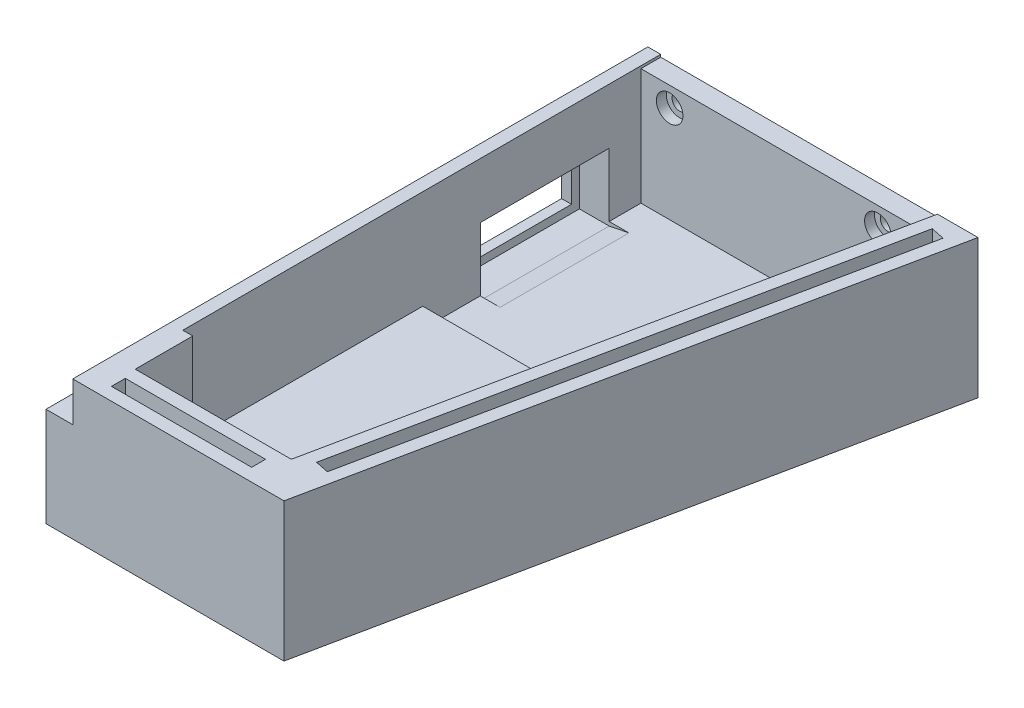
SolidWorks part; units mm, degrees
ref_plane "Front Plane" through (0, 0, 0) normal (1, 0, 0) x (0, 1, 0)
ref_plane "Top Plane" through (0, 0, 0) normal (0, 0, 1) x (0, 1, 0)
ref_plane "Right Plane" through (0, 0, 0) normal (0, 1, 0) x (-1, 0, 0)
sketch "Sketch1" plane through (0, 0, 0) normal (0, 1, 0) x (-1, 0, 0)
  line L0 (-13.4363, 2.5951) -> (16.5637, 147.5951)
  line L1 (-13.4363, -4.9049) -> (-8.4363, -4.9049)
  line L2 (-13.4363, -4.9049) -> (-13.4363, 2.5951)
  line L3 (-13.4363, 2.5951) -> (-8.4363, 2.5951)
  line L4 (-8.4363, -4.9049) -> (-8.4363, 2.5951)
  line L13 (-13.4363, 2.5951) -> (16.5637, 147.5951)
  line L14 (-13.4363, 2.5951) -> (-3.6437, 0.569)
  line L15 (-13.4363, 2.5951) -> (66.5637, 2.5951) construction
  line L16 (-13.4363, 2.5951) -> (-13.4363, 137.5951) construction
  line L17 (-13.4363, 137.5951) -> (66.5637, 137.5951) construction
  line L18 (66.5637, 2.5951) -> (66.5637, 137.5951) construction
  line L19 (66.5637, 137.5951) -> (16.5637, 137.5951)
  line L20 (66.5637, 137.5951) -> (66.5637, 147.5951)
  line L21 (66.5637, 147.5951) -> (16.5637, 147.5951)
  line L22 (16.5637, 137.5951) -> (16.5637, 147.5951)
  line L23 (16.5637, 147.5951) -> (26.3563, 145.569)
  line L24 (-3.6437, 0.569) -> (26.3563, 145.569)
  line L25 (-8.4363, 2.5951) -> (-3.2246, 2.5951)
  line L27 (-3.2246, 2.5951) -> (66.5637, 2.5951)
  line L28 (-3.2246, 2.5951) -> (-3.2246, 7.5951)
  line L29 (-3.2246, 7.5951) -> (66.5637, 7.5951)
  line L30 (66.5637, 2.5951) -> (66.5637, 7.5951)
  line L35 (66.5637, 147.5951) -> (76.5637, 147.5951)
  line L36 (66.5637, 147.5951) -> (66.5637, 2.5951)
  line L37 (66.5637, 2.5951) -> (76.5637, 2.5951)
  line L38 (76.5637, 147.5951) -> (76.5637, 2.5951)
  dimension "D1" = 7.5
  dimension "D3" = 135
  dimension "D4" = 80
  dimension "D5" = 10
  dimension "D7" = 10
  dimension "D9" = 5
  dimension "D8" = 10
  dimension "D6" = 50
extrude "Boss-Extrude1" add sketch "Sketch1" along normal blind 35 contours L24 L19 L20 L21 L23 | L19 L24 L23 L22 | L28 L29 L24 L19 L22 L0 L3 L25 | L38 L35 L20 L36 L30 L37 | L29 L28 L24 | L27 L30 L29 L24 region at (-5.7274, 0, 70.7433) region at (-20.91, 0, 142.2574) region at (-45.5816, 0, 142.6608) region at (-71.5637, 0, 75.0951) region at (2.8797, 0, 5.9284) region at (-31.9275, 0, 5.0889)
sketch "Sketch3" plane through (0, 0, 0) normal (0, -1, 0) x (1, 0, 0)
  line L0 (-76.5637, 147.5951) -> (-16.5637, 147.5951)
  line L1 (-16.5637, 147.5951) -> (13.4363, 2.5951)
  line L2 (13.4363, 2.5951) -> (-76.5637, 2.5951)
  line L3 (-76.5637, 2.5951) -> (-76.5637, 147.5951)
extrude "Boss-Extrude2" add sketch "Sketch3" against normal blind 10
sketch "Sketch4" plane through (0, 35, 0) normal (0, 1, 0) x (-1, 0, 0)
  line L0 (24.7065, 137.5951) -> (-3.2246, 2.5951)
  line L1 (24.7065, 137.5951) -> (66.5637, 137.5951)
  line L2 (24.7065, 137.5951) -> (24.7065, 147.5951)
  line L3 (24.7065, 147.5951) -> (66.5637, 147.5951)
  line L4 (66.5637, 137.5951) -> (66.5637, 147.5951)
  line L5 (24.7065, 137.5951) -> (14.9139, 139.6211)
  line L6 (-3.2246, 2.5951) -> (-13.0172, 4.6211)
  line L7 (14.9139, 139.6211) -> (-13.0172, 4.6211)
  line L8 (-13.4363, 2.5951) -> (76.5637, 2.5951) construction
  line L9 (20.8654, 135.071) -> (-5.7487, 6.4361)
  line L10 (-5.7487, 6.4361) -> (-9.1761, 7.1453)
  line L11 (17.438, 135.7801) -> (-9.1761, 7.1453)
  line L12 (20.8654, 135.071) -> (17.438, 135.7801)
  line L13 (27.9565, 140.8451) -> (27.9565, 144.3451)
  line L14 (27.9565, 144.3451) -> (63.3137, 144.3451)
  line L15 (63.3137, 140.8451) -> (63.3137, 144.3451)
  line L16 (27.9565, 140.8451) -> (63.3137, 140.8451)
  line L17 (76.5637, 147.5951) -> (16.5637, 147.5951) construction
  line L18 (17.438, 135.7801) -> (19.8825, 147.5951)
  line L19 (-2.1901, 7.5951) -> (24.7065, 137.5951) construction
  line L20 (20.8654, 135.071) -> (23.4566, 147.5951)
  line L21 (23.4566, 147.5951) -> (19.8825, 147.5951)
  line L22 (27.9565, 144.3451) -> (19.2101, 144.3451)
  line L23 (19.2101, 144.3451) -> (18.4859, 140.8451)
  line L24 (18.4859, 140.8451) -> (27.9565, 140.8451)
  line L25 (-13.4363, 2.5951) -> (16.5637, 147.5951) construction
  point P4 (-13.4363, 2.5951)
  point P5 (-3.1129, 2.5951)
  dimension "D1" = 3.25
extrude "Cut-Extrude1" cut sketch "Sketch4" against normal blind 10 contours L9 L12 L11 L10 | L13 L16 L15 L14 region at (-45.6351, 35, 142.5951) region at (-5.8447, 35, 71.1081)
sketch "Sketch5" plane through (0, 35, -3.0299) normal (0, -1, 0) x (1, 0, 0)
  line L5 (13.4363, 5.625) -> (-76.5637, 5.625) construction
  line L6 (-66.5637, 10.625) -> (2.1901, 10.625)
  line L7 (-66.5637, 10.625) -> (-66.5637, 5.625)
  line L8 (-66.5637, 5.625) -> (2.1901, 5.625)
  line L9 (2.1901, 10.625) -> (2.1901, 5.625)
  line L10 (2.1901, 10.625) -> (3.2246, 5.625)
  line L11 (2.1901, 10.625) -> (-24.7065, 140.625) construction
  line L12 (3.2246, 5.625) -> (2.1901, 5.625)
  line M9 (-66.5637, 10.625) -> (2.1901, 10.625)
  line M14 (13.4363, 5.625) -> (-76.5637, 5.625)
extrude "Cut-Extrude2" cut sketch "Sketch5" along normal blind 0.625 contours L9 L10 M14 | L9 L7 M9 M14 region at (-32.1868, 35, 5.0951) region at (2.5349, 35, 4.2617)
sketch "Sketch6" plane through (0, 0, 7.5951) normal (0, 0, 1) x (1, 0, 0)
  line L1 (-66.5637, 34.375) -> (-59.3137, 34.375) construction
  line L2 (-66.5637, 34.375) -> (-66.5637, 29.375) construction
  line L3 (-66.5637, 29.375) -> (-59.3137, 29.375) construction
  line L4 (-59.3137, 34.375) -> (-59.3137, 29.375) construction
  circle A0 centre (-59.3137, 29.375) radius 1.9
  dimension "D3" = 3.8
  dimension "D1" = 7.25
extrude "Cut-Extrude3" cut sketch "Sketch6" against normal up to next
sketch "Sketch7" plane through (0, 0, 7.5951) normal (0, 0, 1) x (1, 0, 0)
  circle A0 centre (-59.3137, 29.375) radius 3.35
  dimension "D1" = 6.7
extrude "Cut-Extrude4" cut sketch "Sketch7" against normal blind 2.5
pattern_linear "LPattern1" count 2 spacing 52.5 along (1, 0, 0) of "Cut-Extrude4", "Cut-Extrude3"
sketch "Sketch8" plane through (0, 35, 0) normal (0, 1, 0) x (-1, 0, 0)
  line L0 (76.5637, 147.5951) -> (16.5637, 147.5951) construction
  line L1 (66.5637, 2.5951) -> (69.8137, 2.5951)
  line L2 (66.5637, 2.5951) -> (66.5637, 147.5951)
  line L3 (66.5637, 147.5951) -> (69.8137, 147.5951)
  line L4 (69.8137, 2.5951) -> (69.8137, 147.5951)
  line L5 (66.5637, 2.5951) -> (76.5637, 2.5951) construction
  line L6 (76.5637, 147.5951) -> (73.3137, 147.5951)
  line L7 (76.5637, 147.5951) -> (76.5637, 2.5951)
  line L8 (76.5637, 2.5951) -> (73.3137, 2.5951)
  line L9 (73.3137, 147.5951) -> (73.3137, 2.5951)
  line L11 (73.3137, 2.5951) -> (69.8137, 2.5951)
  line L12 (73.3137, 2.5951) -> (73.3137, 147.5951)
  line L13 (73.3137, 147.5951) -> (69.8137, 147.5951)
  line L14 (69.8137, 2.5951) -> (69.8137, 147.5951)
  line M8 (66.5637, 2.5951) -> (76.5637, 2.5951)
  line M9 (76.5637, 2.5951) -> (76.5637, 147.5951)
  line M10 (76.5637, 147.5951) -> (16.5637, 147.5951)
  dimension "D1" = 3.25
  dimension "D2" = 3.25
extrude "Cut-Extrude5" cut sketch "Sketch8" against normal blind 10 contours L9 L4 M10 M8 | L9 M10 M8 M9 region at (-71.5637, 35, 75.0951) region at (-74.9387, 35, 75.0951)
sketch "Sketch10" plane through (0, 10, 0) normal (0, 1, 0) x (-1, 0, 0)
  line L9 (66.5637, 7.5951) -> (-2.1901, 7.5951) construction
  line L14 (66.5637, 7.5951) -> (26.5637, 7.5951)
  line L15 (66.5637, 7.5951) -> (66.5637, 62.5951)
  line L16 (66.5637, 62.5951) -> (26.5637, 62.5951)
  line L17 (26.5637, 7.5951) -> (26.5637, 62.5951)
  line L18 (66.5637, 7.5951) -> (66.5637, 2.5951) construction
  line L19 (26.5637, 62.5951) -> (15.1843, 7.5951)
  line L20 (15.1843, 7.5951) -> (26.5637, 7.5951)
  line L21 (-3.2246, 2.5951) -> (24.7065, 137.5951) construction
  line M16 (-2.1901, 7.5951) -> (66.5637, 7.5951)
  line M17 (66.5637, 7.5951) -> (66.5637, 137.5951)
  dimension "D1" = 40
  dimension "D2" = 55
extrude "Cut-Extrude6" cut sketch "Sketch10" against normal blind 5 contours L17 L19 M16 | L17 L16 M16 M17 region at (-46.5637, 10, 35.0951) region at (-22.7706, 10, 25.9284)
sketch "Sketch9" plane through (-76.5637, 0, 0) normal (-1, 0, 0) x (0, -1, 0)
  line L1 (0, 2.5951) -> (-6, 2.5951) construction
  line L2 (0, 2.5951) -> (0, 17.5951) construction
  line L3 (0, 17.5951) -> (-6, 17.5951) construction
  line L4 (-6, 2.5951) -> (-6, 17.5951) construction
  line L5 (-6, 17.5951) -> (-19, 17.5951)
  line L6 (-6, 17.5951) -> (-6, 46.0951)
  line L7 (-6, 46.0951) -> (-19, 46.0951)
  line L8 (-19, 17.5951) -> (-19, 46.0951)
  dimension "D3" = 28.5
  dimension "D4" = 13
extrude "Cut-Extrude7" cut sketch "Sketch9" against normal up to next
sketch "Sketch11" plane through (-66.5637, 0, 0) normal (1, 0, 0) x (0, 1, 0)
  line L0 (4, 48.0951) -> (4, 15.5951)
  line L1 (6, 46.0951) -> (19, 46.0951)
  line L2 (6, 46.0951) -> (6, 17.5951)
  line L3 (6, 17.5951) -> (19, 17.5951)
  line L4 (19, 46.0951) -> (19, 17.5951)
  line L5 (4, 15.5951) -> (21, 15.5951)
  line L6 (21, 48.0951) -> (21, 15.5951)
  line L7 (4, 48.0951) -> (21, 48.0951)
  dimension "D1" = 2
extrude "Cut-Extrude8" cut sketch "Sketch11" against normal blind 7.5
chamfer "Chamfer1" distance 1 distance2 5 1 edges at (-66.5637, 5, 31.8451) first distance on face at (-66.5637, 4.5, 31.8451)
sketch "Sketch14" plane through (-66.5637, 0, 0) normal (1, 0, 0) x (0, 1, 0)
  line L0 (10, 62.5951) -> (10, 137.5951) construction
  line L1 (35, 137.5951) -> (10, 137.5951)
  line L2 (35, 137.5951) -> (35, 123.0951)
  line L3 (35, 123.0951) -> (10, 123.0951)
  line L4 (10, 137.5951) -> (10, 123.0951)
  dimension "D1" = 14.5
extrude "Boss-Extrude3" add sketch "Sketch14" along normal blind 2.5
sketch "Sketch13" plane through (-69.8137, 0, 0) normal (-1, 0, 0) x (0, -1, 0)
  line L1 (-25, 147.5951) -> (-30, 147.5951) construction
  line L2 (-25, 147.5951) -> (-25, 130.3451) construction
  line L3 (-25, 130.3451) -> (-30, 130.3451) construction
  line L4 (-30, 147.5951) -> (-30, 130.3451) construction
  circle A0 centre (-30, 130.3451) radius 2.4
  dimension "D3" = 4.8
  dimension "D1" = 17.25
extrude "Cut-Extrude9" cut sketch "Sketch13" against normal blind 3.8
equation "\"whitekey_cutout_length\"= 101.5"
equation "\"whitekey_spacing\"=1.25"
equation "\"key_mount_recess_length\"=50"
equation "\"key_mount_recess_height\"=12.5"
equation "\"key_mount_recess_depth\"=1.5"
equation "\"wall_thickness\"=10"
equation "\"guide_brace_height\"=20"
equation "\"guide_brace_thickness\"=2"
equation "\"dowel_recess_depth\"=10"
equation "\"dowel_recess_offset\"=3.25"
equation "\"dowel_insert_tolerance\"=0.1"
equation "\"base_mount_height\"=40"
equation "\"base_rear_length\"=80"
equation "\"base_front_length\"=111.5"
equation "\"screw_hole_wall_offset\"=7.25"
equation "\"screw_hole_edge_inset\"=\"dowel_recess_depth\"/2"
equation "\"screw_hole_diameter\"=3.8"
equation "\"screw_head_hole_diameter\"=6.7"
equation "\"screw_nut_hole_side_len\"=3.5"
equation "\"screw_nut_recess_offset\"=0.35"
equation "\"screw_head_and_nut_recess_depth\"=2.5"
equation "\"screw_shaft_diameter\"=3.5"
equation "\"switch_board_width\"=30"
equation "\"switch_board_thickness\"=1.6"
equation "\"switch_board_wall_offset\"=11.5"
equation "\"heatset_insert_hole_diameter\"=4.8"
equation "\"heatset_insert_hole_depth\"=3.8"
equation "\"front_rear_panel_width\"=23.75"
equation "\"front_panel_height\"=24"
equation "\"front_rear_panel_recess_depth\"=5"
equation "\"rod_diameter\"=5"
equation "\"rod_head_diameter\"=8"
equation "\"rod_length_adj\"=0.5"
equation "\"rod_insert_length\"=2.8"
equation "\"switch_black_key_mount_height\"=8"
equation "\"switch_white_key_mount_height\"=3"
equation "\"side_panel_depth\"=35"
equation "\"D5@Sketch1\"=\"wall_thickness\""
equation "\"D7@Sketch1\"=\"wall_thickness\""
equation "\"D8@Sketch1\"=\"wall_thickness\""
equation "\"D9@Sketch1\"=\"wall_thickness\"/2"
equation "\"D2@Sketch1\"=\"wall_thickness\"/2"
equation "\"D1@Sketch1\"=\"wall_thickness\"*0.75"
equation "\"D3@Sketch1\"=\"interface_panel_height\""
equation "\"D4@Sketch1\"=\"base_rear_length\""
equation "\"D1@Boss-Extrude1\"=\"side_panel_depth\""
equation "\"D1@Boss-Extrude2\"=\"wall_thickness\""
equation "\"D1@Sketch4\"=\"dowel_recess_offset\""
equation "\"D1@Cut-Extrude1\"=\"dowel_recess_depth\""
equation "\"D1@Sketch6\"=\"screw_hole_wall_offset\""
equation "\"D2@Sketch6\"=\"screw_hole_edge_inset\""
equation "\"D3@Sketch6\"=\"screw_hole_diameter\""
equation "\"D1@Sketch7\"=\"screw_head_hole_diameter\""
equation "\"D3@LPattern1\"=\"base_rear_length\"-\"wall_thickness\"-\"screw_hole_wall_offset\"*2-3"
equation "\"D1@Sketch8\"=\"dowel_recess_offset\""
equation "\"D2@Sketch8\"=\"dowel_recess_offset\""
equation "\"D1@Cut-Extrude5\"=\"front_rear_panel_recess_depth\"*2"
equation "\"D1@Cut-Extrude2\"=\"whitekey_spacing\"/2"
equation "\"interface_panel_height\"=135"
equation "\"interface_panel_roof_length\"=50"
equation "\"D6@Sketch1\"=\"interface_panel_roof_length\""
equation "\"D2@Sketch9\"=\"wall_thickness\"*0.6"
equation "\"D1@Sketch9\"=\"wall_thickness\"*1.5"
equation "\"D1@Sketch10\"=\"base_rear_length\"/2"
equation "\"D2@Sketch10\"=\"interface_panel_height\"/3+\"wall_thickness\""
equation "\"D1@Cut-Extrude6\"=\"wall_thickness\"/2"
equation "\"D1@Cut-Extrude8\"=\"wall_thickness\"*0.75"
equation "\"D1@Sketch13\"=\"wall_thickness\"+\"screw_hole_wall_offset\""
equation "\"D2@Sketch13\"=\"screw_hole_edge_inset\""
equation "\"D3@Sketch13\"=\"heatset_insert_hole_diameter\""
equation "\"D1@Sketch14\"=\"screw_hole_wall_offset\"*2"
equation "\"D1@Boss-Extrude3\"=\"wall_thickness\"/4"
equation "\"D1@Cut-Extrude9\"=\"heatset_insert_hole_depth\""
